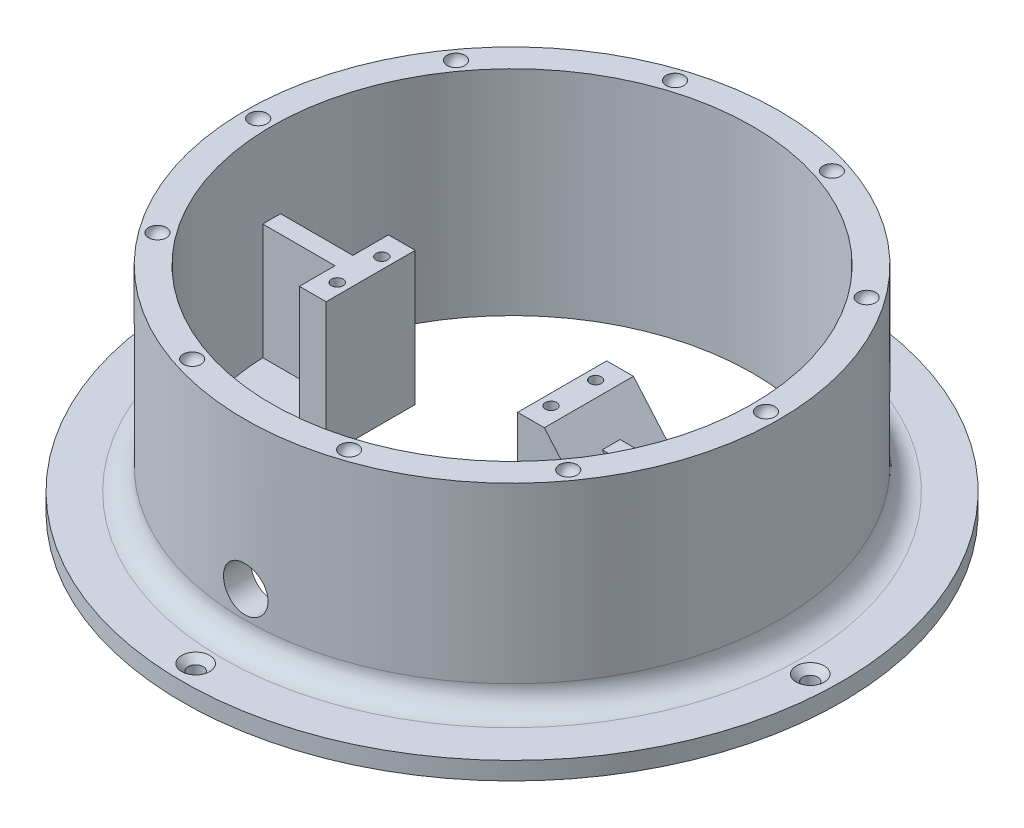
SolidWorks part; units mm, degrees
ref_plane "Front Plane" through (0, 0, 0) normal (0, 0, 1) x (1, 0, 0)
ref_plane "Top Plane" through (0, 0, 0) normal (0, 1, 0) x (1, 0, 0)
ref_plane "Right Plane" through (0, 0, 0) normal (1, 0, 0) x (0, 0, -1)
sketch "Sketch1" plane through (0, 0, 0) normal (0, 0, 1) x (1, 0, 0)
  line L0 (0, 0) -> (0, 49.9699) construction
  line L4 (54, 0) -> (54, 48)
  line L6 (54, 48) -> (60, 48)
  line L7 (54, 0) -> (74, 0)
  line L8 (74, 0) -> (74, 4)
  line L9 (60, 48) -> (60, 4)
  line L10 (74, 4) -> (60, 4)
  dimension "D1" = 6
  dimension "D2" = 48
  dimension "D3" = 20
  dimension "D4" = 4
  dimension "D5" = 60
revolve "Revolve2" add sketch "Sketch1" angle 360 about L0
fillet "Fillet1" radius 5 1 edges at (0, 4, -60)
sketch "Sketch5" plane through (0, 0, 0) normal (0, 1, 0) x (1, 0, 0)
  line L0 (2.0449, 0) -> (2.0449, 69)
  line L1 (-26.4, 0) -> (26.4, 0) construction
  dimension "D1" = 69
hole_wizard "CSK for M3 Countersunk Raised Head Screw1" positions "Sketch7" profile "Sketch8" countersink size "M3" standard "ISO" end condition through all
sketch "Sketch7" plane through (0, 4, 0) normal (0, 1, 0) x (1, 0, 0)
  point P0 (2.0449, 69)
sketch "Sketch8" plane through (2.0449, 4, -69) normal (1, 0, 0) x (0, 0, 1)
  line L0 (0, 0) -> (0, 4)
  line L1 (0, 4) -> (1.7, 4)
  line L2 (1.7, 4) -> (1.7, 1.45)
  line L3 (1.7, 1.45) -> (3.15, 0)
  line L5 (3.15, 0) -> (0, 0)
  line L6 (-1.7, 1.45) -> (-3.15, 0) construction
  line L11 (0, -6.35) -> (0, 107.95) construction
  dimension "Thru Hole Dia." = 3.4
  dimension "Thru Hole Depth" = 4
  dimension "Near C'Sink Dia." = 6.3
  dimension "Near C'Sink Angle" = 90
pattern_circular "CirPattern2" count 4 over 360 about axis through (0, 4, 0) along (0, -1, 0) of "CSK for M3 Countersunk Raised Head Screw1"
sketch "Sketch10" plane through (0, 0, 0) normal (0, 0, 1) x (1, 0, 0)
  line L0 (57, 46) -> (57, 50)
  line L4 (60, 48) -> (-60, 48) construction
  arc A1 (57, 46) -> (57, 50) centre (57, 48) ccw
  dimension "D1" = 57
  dimension "D2" = 4
revolve "Cut-Revolve3" cut sketch "Sketch10" angle 360 about L0
pattern_circular "CirPattern3" count 10 over 360 about axis through (0, 0, 0) along (0, -1, 0) of "Cut-Revolve3"
sketch "Sketch11" plane through (0, 0, 0) normal (0, 0, 1) x (1, 0, 0)
  line L0 (22.25, 0) -> (56.25, 0)
  line L1 (-54, 0) -> (54, 0) construction
  line L2 (22.25, 0) -> (22.25, 6.8907)
  line L3 (-74, 0) -> (74, 0) construction
  line L4 (56.25, 0) -> (56.25, 4)
  line L5 (11.25, 20) -> (22.25, 6.8907)
  line L6 (-37.75, 30) -> (-37.75, 4)
  line L7 (74, 4) -> (-74, 4) construction
  line L8 (56.25, 4) -> (30.25, 4)
  line L9 (11.25, 30) -> (11.25, 20)
  line L10 (30.25, 14.9389) -> (17.25, 30)
  line L11 (11.25, 30) -> (17.25, 30)
  line L12 (30.25, 14.9389) -> (30.25, 4)
  line L13 (-31.75, 30) -> (-31.75, 0)
  line L14 (-31.75, 0) -> (-56.75, 0)
  line L15 (-56.75, 0) -> (-56.75, 4)
  line L16 (-31.75, 30) -> (-37.75, 30)
  line L17 (-56.75, 4) -> (-37.75, 4)
  dimension "D1" = 22.25
  dimension "D2" = 11.25
  dimension "D3" = 140
  dimension "D4" = 6
  dimension "D5" = 10
  dimension "D6" = 4
  dimension "D7" = 34
  dimension "D8" = 6
  dimension "D9" = 4
  dimension "D10" = 25
  dimension "D11" = 43
  dimension "D12" = 30
extrude "Boss-Extrude1" add sketch "Sketch11" along normal mid plane 20 contours L6 L17 L15 L14 L13 L16 | L10 L11 L9 L5 L2 L0 L4 L8 L12
sketch "Sketch14" plane through (0, 30, 0) normal (0, 1, 0) x (1, 0, 0)
  line L0 (-31.75, -10) -> (-31.75, 10) construction
  line L1 (-26.4, 0) -> (26.4, 0) construction
  circle A0 centre (-34.25, 5) radius 1.3
  circle A1 centre (-34.25, -5) radius 1.3
  circle A2 centre (13.75, 5) radius 1.3
  circle A3 centre (13.75, -5) radius 1.3
  dimension "D1" = 2.6
  dimension "D5" = 2.6
  dimension "D2" = 2.5
  dimension "D3" = 48
  dimension "D4" = 5
extrude "Cut-Extrude1" cut sketch "Sketch14" against normal blind 8
sketch "Sketch15" plane through (0, 0, 0) normal (0, 0, 1) x (1, 0, 0)
  line L0 (-74, 0) -> (74, 0) construction
  line L2 (-37.75, 30) -> (-56.75, 30)
  dimension "D1" = 19
  dimension "D2" = 37.75
  dimension "D3" = 30
rib "Rib1" sketch "Sketch15" sketch "Sketch15" thickness 4 extrusion direction parallel to sketch draft on no parameters "D1"=4
sketch "Sketch16" plane through (0, 0, 0) normal (0, 0, 1) x (1, 0, 0)
  line L2 (30.25, 14.9389) -> (17.25, 30) construction
  line L3 (22.25, 24.2073) -> (56.25, 24.2073)
  dimension "D1" = 22.25
  dimension "D2" = 34
rib "Rib2" sketch "Sketch16" sketch "Sketch16" thickness 4 extrusion direction parallel to sketch draft on no parameters "D1"=4
sketch "Sketch17" plane through (0, 0, 0) normal (0, 0, 1) x (1, 0, 0)
  circle A0 centre (0, 15) radius 5
  dimension "D1" = 15
  dimension "D2" = 10
extrude "Cut-Extrude3" cut sketch "Sketch17" along normal up to next
